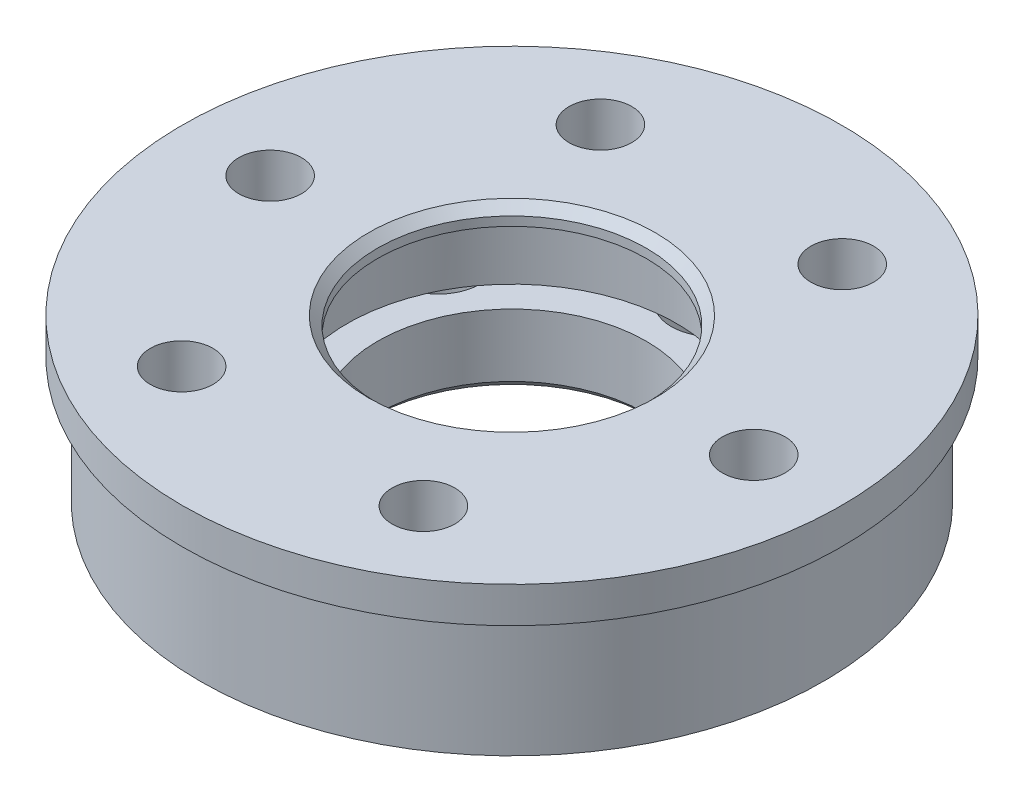
SolidWorks part; units mm, degrees
ref_plane "Front Plane" through (0, 0, 0) normal (0, 0, 1) x (1, 0, 0)
ref_plane "Top Plane" through (0, 0, 0) normal (0, 1, 0) x (1, 0, 0)
ref_plane "Right Plane" through (0, 0, 0) normal (1, 0, 0) x (0, 0, -1)
sketch "Sketch1" plane through (0, 0, 0) normal (0, 1, 0) x (1, 0, 0)
  circle A0 centre (0, 0) radius 13.5 construction
  circle A1 centre (13.5, 0) radius 1.75
  circle A2 centre (6.75, -11.6913) radius 1.75
  circle A3 centre (-6.75, -11.6913) radius 1.75
  circle A4 centre (-13.5, 0) radius 1.75
  circle A5 centre (-6.75, 11.6913) radius 1.75
  circle A6 centre (6.75, 11.6913) radius 1.75
  circle A7 centre (0, 0) radius 17.4
  circle A8 centre (0, 0) radius 7.5
  point P17 (0, 0)
  dimension "D1" = 27
  dimension "D2" = 3.5
  dimension "D4" = 34.8
  dimension "D5" = 15
  dimension "D3" = 6
extrude "Boss-Extrude1" add sketch "Sketch1" along normal mid plane 9
sketch "Sketch2" plane through (0, 0, 0) normal (0, 1, 0) x (1, 0, 0)
  circle A0 centre (0, 0) radius 9.2
  dimension "D1" = 18.4
extrude "Cut-Extrude1" cut sketch "Sketch2" along normal blind 4 from offset 0.5 offset against normal yes
sketch "Sketch3" plane through (0, -4.5, 0) normal (0, -1, 0) x (1, 0, 0)
  circle A0 centre (0, 0) radius 11.75
  circle A1 centre (0, 0) radius 15.25
  circle A2 centre (-13.5, 0) radius 1.75 construction
extrude "Boss-Extrude2" add sketch "Sketch3" against normal blind 1.5
chamfer "Chamfer1" distance 0.5 angle 45 2 edges at (0, -4.5, 7.5) (0, 4.5, 7.5)
sketch "Sketch4" plane through (0, 4.5, 0) normal (0, 1, 0) x (1, 0, 0)
  circle A0 centre (0, 0) radius 18.4
  circle A1 centre (0, 0) radius 17.4 construction
  circle A2 centre (0, 0) radius 17.4
  dimension "D1" = 1
extrude "Boss-Extrude3" add sketch "Sketch4" against normal blind 2
sketch "Sketch5" plane through (0, -4.5, 0) normal (0, -1, 0) x (-1, 0, 0)
  line L0 (0, 0) -> (-9.7428, -5.625) construction
  line L1 (0, 0) -> (-11.25, 0) construction
  circle A0 centre (0, 0) radius 11.25 construction
  circle A1 centre (-9.7428, -5.625) radius 2.35
  circle A2 centre (-9.7428, 5.625) radius 2.35
  circle A3 centre (0, 11.25) radius 2.35
  circle A4 centre (9.7428, 5.625) radius 2.35
  circle A5 centre (9.7428, -5.625) radius 2.35
  circle A6 centre (0, -11.25) radius 2.35
  point P18 (0, 0)
  dimension "D1" = 4.7
  dimension "D2" = 22.5
  dimension "D3" = 30
  dimension "D4" = 6
extrude "Cut-Extrude2" cut sketch "Sketch5" against normal blind 4
chamfer "Chamfer2" [suppressed] distance 3 angle 45
equation "\"D5@Sketch1\"=18-3"
